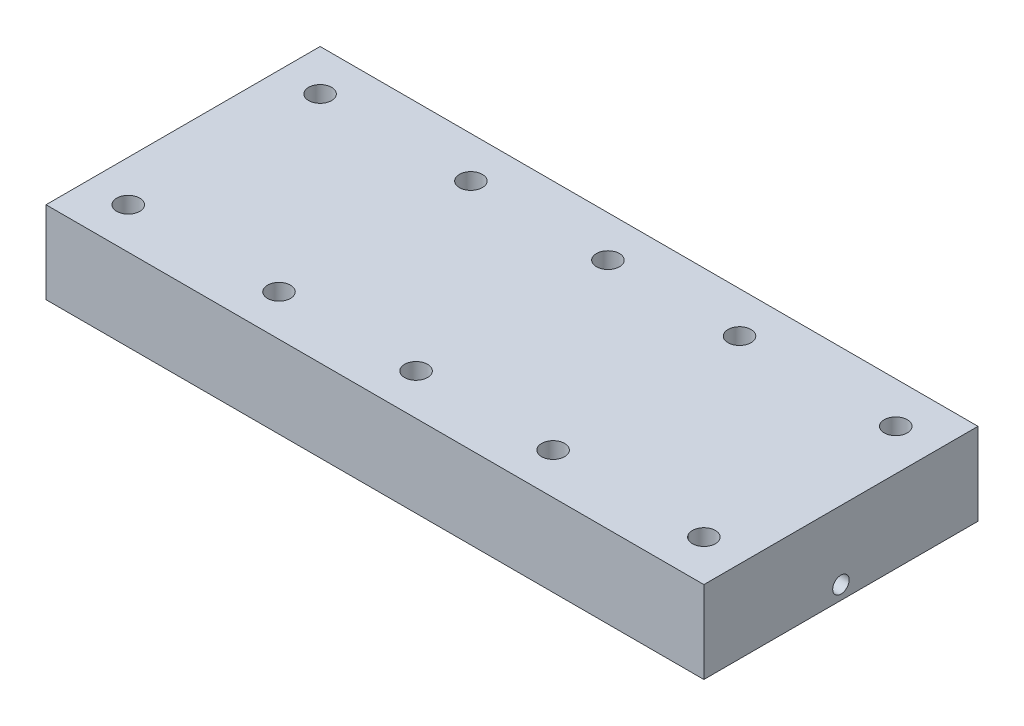
SolidWorks part; units mm, degrees
ref_plane "Front Plane" through (0, 0, 0) normal (0, 0, 1) x (1, 0, 0)
ref_plane "Top Plane" through (0, 0, 0) normal (0, 1, 0) x (1, 0, 0)
ref_plane "Right Plane" through (0, 0, 0) normal (1, 0, 0) x (0, 0, -1)
sketch "Sketch2" plane through (0, 0, 0) normal (0, 1, 0) x (1, 0, 0)
  line L0 (-46.8981, 34.5466) -> (-46.8981, -15.4534)
  line L1 (-46.8981, -15.4534) -> (73.1019, -15.4534)
  line L2 (73.1019, -15.4534) -> (73.1019, 34.5466)
  line L3 (73.1019, 34.5466) -> (-46.8981, 34.5466)
  dimension "D1" = 120
  dimension "D2" = 50
extrude "Boss-Extrude1" add sketch "Sketch2" along normal blind 15
sketch "Sketch3" plane through (0, 0, 0) normal (0, 1, 0) x (1, 0, 0)
  line L0 (74.3548, 9.5466) -> (-56.2815, 9.5466) construction
  line L1 (63.1019, 9.5466) -> (63.1019, 17.0466)
  line L2 (63.1019, 17.0466) -> (3.1019, 17.0466)
  line L3 (3.1019, 17.0466) -> (3.1019, 19.5466)
  line L4 (3.1019, 19.5466) -> (-36.8981, 19.5466)
  line L5 (-36.8981, 19.5466) -> (-36.8981, 9.5466)
  line L6 (-36.8981, 9.5466) -> (63.1019, 9.5466)
  line L7 (73.1019, -15.4534) -> (73.1019, 34.5466) construction
  line L9 (-46.8981, -15.4534) -> (73.1019, -15.4534) construction
  dimension "D1" = 60
  dimension "D2" = 40
  dimension "D3" = 10
  dimension "D4" = 25
  dimension "D5" = 10
  dimension "D6" = 7.5
sketch "Skizze7" plane through (-46.8981, 0, 0) normal (-1, 0, 0) x (0, 0, 1)
  line L1 (-34.5466, 0) -> (15.4534, 0) construction
  line L3 (-9.5466, -6.0172) -> (-9.5466, 6.0172) construction
  line L4 (15.4534, 15) -> (15.4534, 0) construction
  line L5 (-34.5466, 15) -> (-34.5466, 0) construction
  circle A0 centre (-9.5466, 2.5) radius 1.5
  dimension "D1" = 3
  dimension "D2" = 2.5
extrude "Schnitt-Linear austragen6" cut sketch "Skizze7" against normal blind 10
revolve "Schnitt-Rotation1" cut sketch "Sketch3" angle 360 about L0
sketch "Skizze10" plane through (0, 0, 0) normal (0, -1, 0) x (1, 0, 0)
  line L0 (63.1019, -17.0466) -> (3.1019, -17.0466) construction
  line L1 (53.1019, -17.0466) -> (40.6019, -17.0466)
  line L2 (53.1019, -17.0466) -> (53.1019, -15.5466)
  line L3 (53.1019, -15.5466) -> (40.6019, -15.5466)
  line L4 (40.6019, -17.0466) -> (40.6019, -15.5466)
  line L5 (63.1019, -2.0466) -> (63.1019, -17.0466) construction
  line L10 (85.7448, -9.5466) -> (-66.8579, -9.5466) construction
  line L11 (-46.8981, 15.4534) -> (73.1019, 15.4534) construction
  line L12 (73.1019, -34.5466) -> (-46.8981, -34.5466) construction
  dimension "D1" = 10
  dimension "D2" = 12.5
  dimension "D5" = 1.5
revolve "Rotation3" add sketch "Skizze10" angle 180 about L10 reverse direction yes
sketch "Skizze11" plane through (0, 0, 0) normal (0, -1, 0) x (1, 0, 0)
  line L0 (40.6019, -17.0466) -> (3.1019, -17.0466) construction
  line L1 (28.1019, -17.0466) -> (15.6019, -17.0466)
  line L2 (28.1019, -17.0466) -> (28.1019, -15.5466)
  line L3 (28.1019, -15.5466) -> (15.6019, -15.5466)
  line L4 (15.6019, -17.0466) -> (15.6019, -15.5466)
  line L5 (53.1019, -15.5466) -> (40.6019, -15.5466) construction
  line L6 (40.6019, -15.5466) -> (40.6019, -17.0466) construction
  line L7 (95.0378, -9.5466) -> (-94.5432, -9.5466) construction
  line L8 (-46.8981, 15.4534) -> (73.1019, 15.4534) construction
  line L9 (73.1019, -34.5466) -> (-46.8981, -34.5466) construction
  point P10 (40.6019, -16.2966)
  dimension "D1" = 12.5
  dimension "D2" = 12.5
revolve "Rotation4" add sketch "Skizze11" angle 180 about L7 reverse direction yes
sketch "Skizze12" plane through (0, 0, 0) normal (0, -1, 0) x (1, 0, 0)
  line L0 (73.1019, 15.4534) -> (73.1019, -34.5466) construction
  line L1 (-46.8981, -34.5466) -> (-46.8981, 15.4534) construction
  line L3 (-46.8981, 15.4534) -> (73.1019, 15.4534) construction
  circle A0 centre (-39.3981, 7.9534) radius 2.1
  circle A1 centre (13.1019, 7.9534) radius 2.1
  circle A2 centre (65.6019, 7.9534) radius 2.1
  dimension "D3" = 4.2
  dimension "D2" = 7.5
  dimension "D4" = 7.5
  dimension "D5" = 7.5
  dimension "D1" = 3
ref_plane "Ebene6" through (0, 0, -9.5466) normal (0, 0, 1) x (1, 0, 0)
extrude "Schnitt-Linear austragen7" cut sketch "Skizze12" against normal through all
mirror "Spiegeln1" about plane through (0, 0, -9.5466) normal (0, 0, 1) of "Schnitt-Linear austragen7"
sketch "Skizze13" plane through (-46.8981, 0, 0) normal (-1, 0, 0) x (0, 0, 1)
  line L0 (-34.5466, 0) -> (15.4534, 0) construction
  line L1 (15.4534, 15) -> (0.4534, 15)
  line L2 (15.4534, 15) -> (15.4534, 5)
  line L3 (15.4534, 5) -> (0.4534, 5)
  line L4 (0.4534, 15) -> (0.4534, 5)
  line L5 (-34.5466, 0) -> (15.4534, 0) construction
  line L6 (-34.5466, 15) -> (-19.5466, 15)
  line L7 (-34.5466, 15) -> (-34.5466, 5)
  line L8 (-34.5466, 5) -> (-19.5466, 5)
  line L9 (-19.5466, 15) -> (-19.5466, 5)
  dimension "D1" = 15
  dimension "D2" = 5
  dimension "D3" = 15
  dimension "D4" = 5
sketch "Sketch4" plane through (0, 0, 0) normal (0, 1, 0) x (1, 0, 0)
  line L0 (-46.8981, -15.4534) -> (-46.8981, -0.4534) construction
  line L1 (-46.8981, 34.5466) -> (-46.8981, 19.5466) construction
  line L2 (73.1019, -15.4534) -> (73.1019, 34.5466) construction
  line L3 (73.1019, 34.5466) -> (-46.8981, 34.5466) construction
  line L4 (-46.8981, -15.4534) -> (73.1019, -15.4534) construction
  circle A0 centre (-11.8981, 27.0466) radius 2.1
  circle A1 centre (37.1019, 27.0466) radius 2.1
  circle A2 centre (38.1019, -7.9534) radius 2.1
  circle A3 centre (-11.8981, -7.9534) radius 2.1
  dimension "D1" = 4.2
  dimension "D2" = 4.2
  dimension "D3" = 4.2
  dimension "D4" = 4.2
  dimension "D6" = 35
  dimension "D5" = 35
  dimension "D7" = 35
  dimension "D8" = 36
  dimension "D9" = 7.5
  dimension "D10" = 7.5
  dimension "D11" = 7.5
  dimension "D12" = 7.5
extrude "Cut-Extrude1" cut sketch "Sketch4" against normal blind 10 and the other way blind 25
ref_plane "Plane1" through (83.1019, 0, 0) normal (1, 0, 0) x (0, 0, -1)
sketch "Sketch5" plane through (83.1019, 0, 0) normal (1, 0, 0) x (0, 0, -1)
  circle A0 centre (9.5466, 2.5) radius 1.5
  dimension "D1" = 3
extrude "Cut-Extrude2" cut sketch "Sketch5" against normal blind 25
fillet "Fillet2" radius 1 1 edges at (3.1019, 10, -9.5466)
fillet "Fillet3" radius 1 1 edges at (3.1019, 7.5, -9.5466)
fillet "Fillet4" radius 1 1 edges at (15.6019, 7.5, -9.5466)
fillet "Fillet5" radius 1 1 edges at (15.6019, 6, -9.5466)
fillet "Fillet7" radius 1 1 edges at (28.1019, 6, -9.5466)
fillet "Fillet8" radius 1 1 edges at (28.1019, 7.5, -9.5466)
fillet "Fillet9" radius 1 1 edges at (40.6019, 7.5, -9.5466)
fillet "Fillet10" radius 1 1 edges at (40.6019, 6, -9.5466)
fillet "Fillet11" radius 1 1 edges at (53.1019, 6, -9.5466)
fillet "Fillet12" radius 1 1 edges at (53.1019, 7.5, -9.5466)
